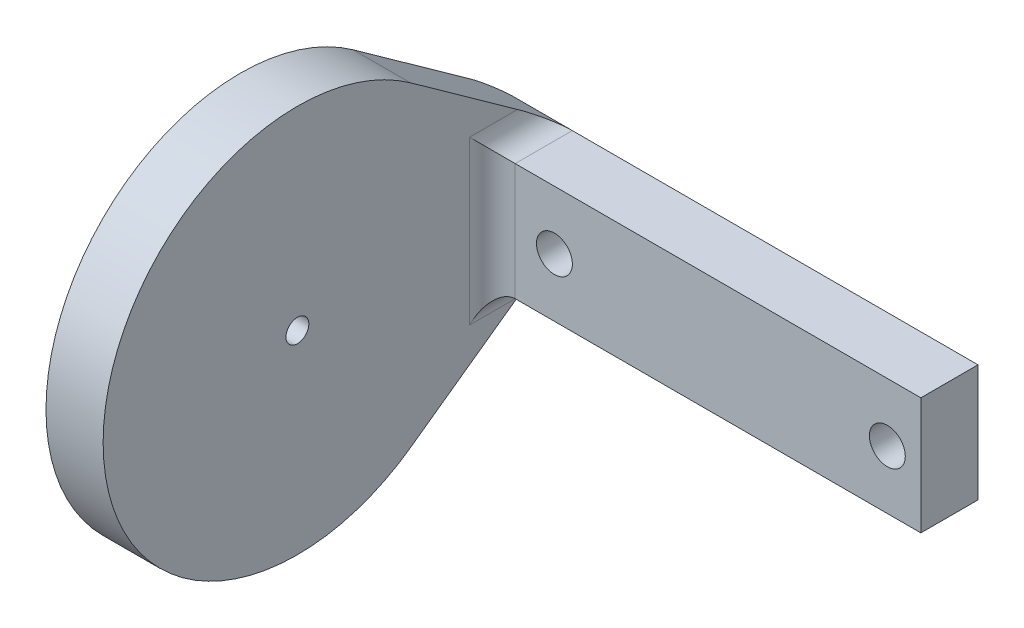
SolidWorks part; units mm, degrees
ref_plane "Front Plane" through (0, 0, 0) normal (0, 0, 1) x (1, 0, 0)
ref_plane "Top Plane" through (0, 0, 0) normal (0, 1, 0) x (1, 0, 0)
ref_plane "Right Plane" through (0, 0, 0) normal (1, 0, 0) x (0, 0, -1)
sketch "Sketch1" plane through (0, 0, 0) normal (0, 0, 1) x (1, 0, 0)
  line L0 (-18.5, 0) -> (18.5, 0)
  line L1 (-22.225, 6.5024) -> (22.225, 6.5024)
  line L2 (-22.225, 6.5024) -> (-22.225, -6.5024) construction
  line L3 (-22.225, -6.5024) -> (22.225, -6.5024)
  line L4 (22.225, 6.5024) -> (22.225, -6.5024)
  line L5 (-22.225, 6.5024) -> (22.225, -6.5024) construction
  line L6 (-22.225, -6.5024) -> (22.225, 6.5024) construction
  line L8 (-22.225, 6.5024) -> (-25.4, 6.5024)
  line L9 (-22.225, 6.5024) -> (-22.225, -6.5024)
  line L10 (-22.225, -6.5024) -> (-25.4, -6.5024)
  line L11 (-25.4, 6.5024) -> (-25.4, -6.5024)
  circle A0 centre (-18.5, 0) radius 1.9939
  circle A1 centre (18.5, 0) radius 1.9939
  point P1 (0, 0)
  point P9 (0, 0)
  dimension "D4" = 3.9878
  dimension "D5" = 3.9878
  dimension "D1" = 13.0048
  dimension "D2" = 44.45
  dimension "D3" = 37
  dimension "D6" = 3.175
extrude "Boss-Extrude1" add sketch "Sketch1" along normal blind 6.35 contours L4 L1 L2 L3 | L9 L8 L11 L10 region at (0, 6.0393, 0)
sketch "Sketch2" plane through (0, 0, 0) normal (0, 0, 1) x (1, 0, 0)
  line L1 (-25.4, 6.5024) -> (-31.75, 6.5024)
  line L2 (-25.4, 6.5024) -> (-25.4, -6.5024)
  line L3 (-25.4, -6.5024) -> (-31.75, -6.5024)
  line L4 (-31.75, 6.5024) -> (-31.75, -6.5024)
  dimension "D1" = 13.0048
  dimension "D2" = 6.35
extrude "Boss-Extrude2" add sketch "Sketch2" along normal blind 38.1
sketch "Sketch3" plane through (-25.4, 0, 0) normal (1, 0, 0) x (0, 0, -1)
  line L0 (-6.35, 0) -> (-28.0162, 0)
  line L1 (-6.35, 6.5024) -> (-6.35, -6.5024) construction
  circle A0 centre (-28.0162, 0) radius 1.27
  dimension "D2" = 2.54
  dimension "D1" = 21.6662
extrude "Cut-Extrude1" cut sketch "Sketch3" against normal blind 50.8 contours A0 region at (-25.4, 0, 29.2503)
sketch "Sketch4" plane through (-31.75, 0, 0) normal (-1, 0, 0) x (0, 0, 1)
  line L0 (0, 6.5024) -> (15.4537, 17.5588)
  line L1 (0, -6.5024) -> (15.4537, -17.5588)
  line L2 (0, 6.5024) -> (0, -6.5024)
  arc A0 (15.4537, -17.5588) -> (15.4537, 17.5588) centre (28.0162, 0) ccw
  dimension "D1" = 43.18
extrude "Boss-Extrude3" add sketch "Sketch4" against normal blind 6.35
sketch "Sketch5" plane through (-25.4, 0, 0) normal (1, 0, 0) x (0, 0, -1)
  line L0 (-6.35, 0) -> (-28.0162, 0)
  line L1 (-6.35, 6.5024) -> (-6.35, -6.5024) construction
  circle A0 centre (-28.0162, 0) radius 1.27
  dimension "D2" = 2.54
  dimension "D1" = 21.6662
extrude "Cut-Extrude2" cut sketch "Sketch5" against normal through all contours A0
fillet "Fillet1" radius 2.54 4 edges at (-31.75, 0, 0) (-25.4, -6.5024, 3.175) (-25.4, 6.5024, 3.175) (-25.4, 0, 6.35)
